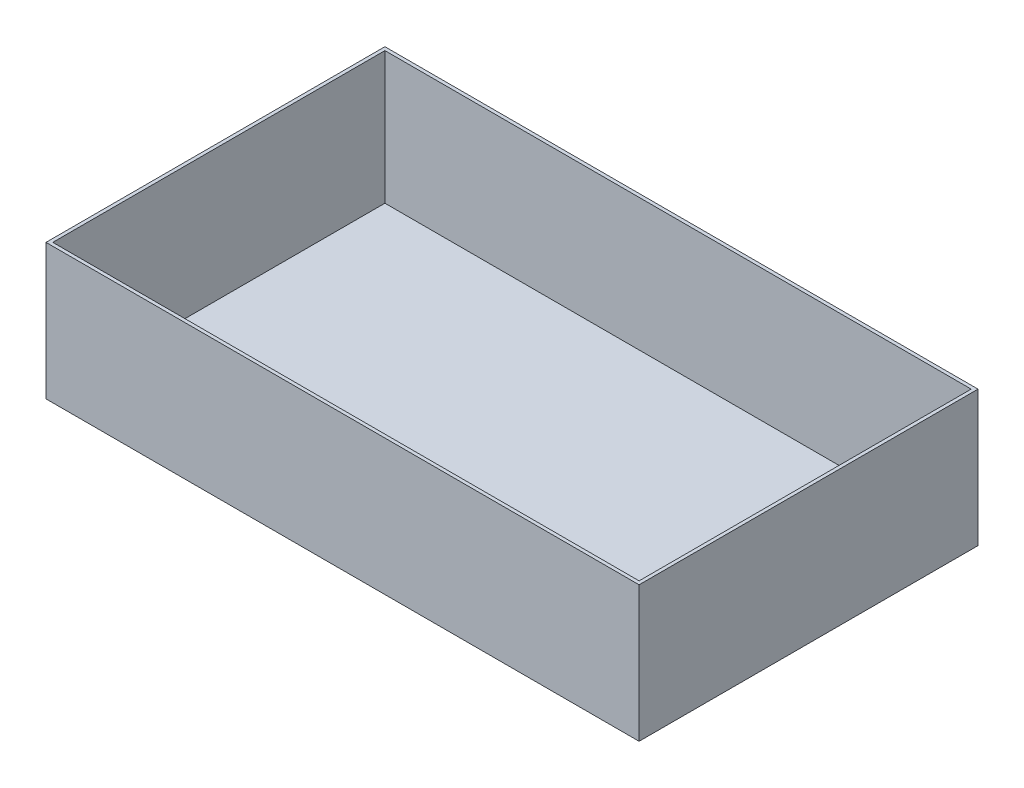
SolidWorks part; units mm, degrees
ref_plane "Front Plane" through (0, 0, 0) normal (0, 0, 1) x (1, 0, 0)
ref_plane "Top Plane" through (0, 0, 0) normal (0, 1, 0) x (1, 0, 0)
ref_plane "Right Plane" through (0, 0, 0) normal (1, 0, 0) x (0, 0, -1)
sketch "Sketch1" plane through (0, 0, 0) normal (0, 1, 0) x (1, 0, 0)
  line L1 (175, -100) -> (-175, -100)
  line L2 (175, -100) -> (175, 100)
  line L3 (175, 100) -> (-175, 100)
  line L4 (-175, -100) -> (-175, 100)
  line L5 (175, -100) -> (-175, 100) construction
  line L6 (175, 100) -> (-175, -100) construction
  point P0 (0, 0)
  point P5 (0, 0)
  dimension "D1" = 200
  dimension "D2" = 350
extrude "Boss-Extrude1" add sketch "Sketch1" along normal blind 80 contours L1 L4 L3 L2
shell "Shell1" thickness 2 removed face at (0, 80, 0)
